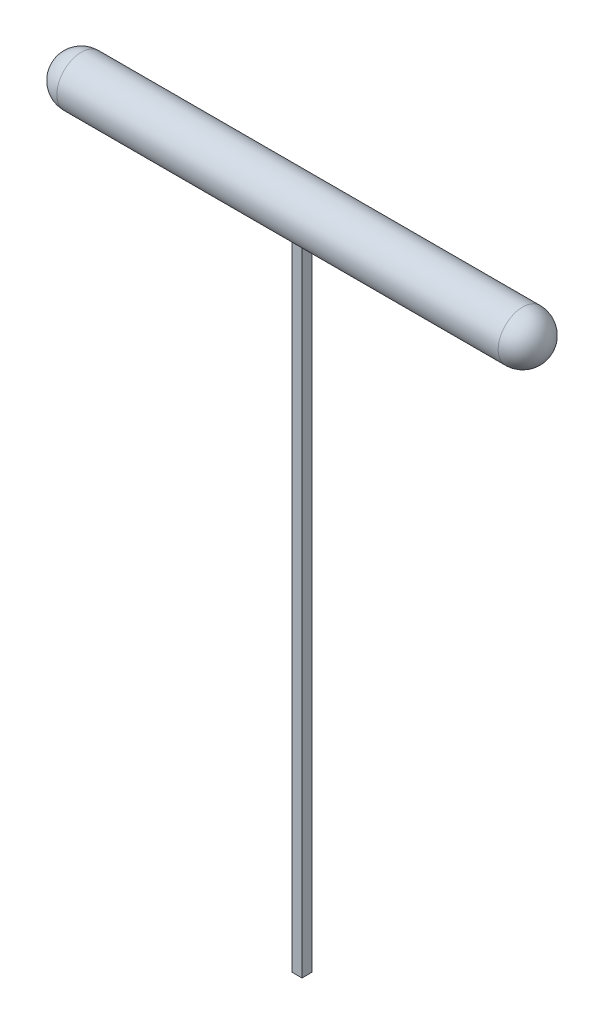
SolidWorks part; units mm, degrees
ref_plane "Front Plane" through (0, 0, 0) normal (0, 0, 1) x (1, 0, 0)
ref_plane "Top Plane" through (0, 0, 0) normal (0, 1, 0) x (1, 0, 0)
ref_plane "Right Plane" through (0, 0, 0) normal (1, 0, 0) x (0, 0, -1)
sketch "Sketch1" plane through (0, 0, 0) normal (0, 0, 1) x (1, 0, 0)
  line L0 (-22.5, 0) -> (22.5, 0) construction
  line L1 (-22.5, 2.5) -> (22.5, 2.5)
  line L2 (-22.5, -2.5) -> (22.5, -2.5)
  line L3 (-25, 0) -> (25, 0)
  line L5 (-0.5, -2.5) -> (0.5, -2.5)
  line L6 (-0.5, -2.5) -> (-0.5, -67.5)
  line L7 (-0.5, -67.5) -> (0.5, -67.5)
  line L8 (0.5, -2.5) -> (0.5, -67.5)
  arc A0 (-22.5, 2.5) -> (-22.5, -2.5) centre (-22.5, 0) ccw
  arc A1 (22.5, -2.5) -> (22.5, 2.5) centre (22.5, 0) ccw
  point P2 (0, 0)
  point P14 (0, -67.5)
  dimension "D1" = 45
  dimension "D2" = 5
  dimension "D3" = 65
  dimension "D4" = 1
revolve "Revolve1" add sketch "Sketch1" angle 360 about L3 region at (0, 1.2348, 0)
extrude "Boss-Extrude1" add sketch "Sketch1<4>" along normal mid plane 1 separate body contours L8 L2 L6 L7 region at (0, -35, 0)
sketch "Sketch1<4>" plane through (0, 0, 0) normal (0, 0, 1) x (1, 0, 0) same geometry as "Sketch1"
